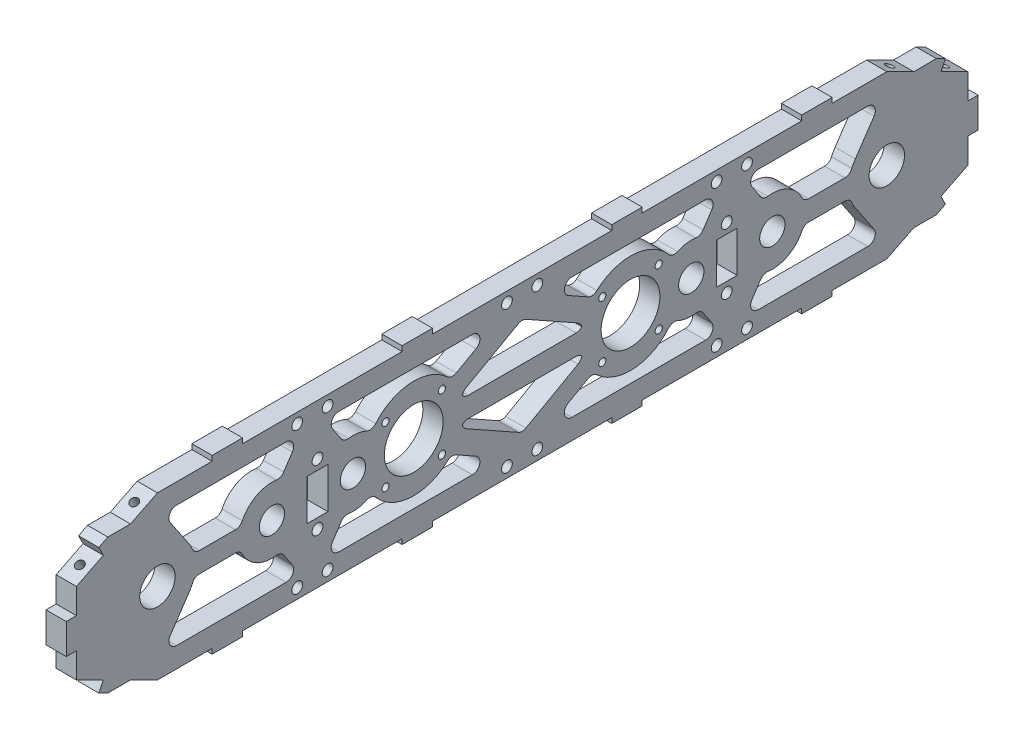
SolidWorks part; units mm, degrees
material "6061-T6 (SS)"
ref_plane "Front Plane" through (0, 0, 0) normal (0, 0, 1) x (1, 0, 0)
ref_plane "Top Plane" through (0, 0, 0) normal (0, 1, 0) x (1, 0, 0)
ref_plane "Right Plane" through (0, 0, 0) normal (1, 0, 0) x (0, 0, -1)
sketch "Sketch1" plane through (0, 0, 0) normal (1, 0, 0) x (0, 0, -1)
  line L0 (-160.655, 50.8) -> (93.345, 50.8)
  line L1 (93.345, 50.8) -> (93.345, -50.8)
  line L2 (93.345, -50.8) -> (-160.655, -50.8)
  line L3 (93.345, 0) -> (55.245, 50.8)
  line L4 (93.345, 0) -> (55.245, -50.8)
  circle A0 centre (0, 0) radius 38.1
  circle A1 centre (0, 0) radius 7.9375
  circle A2 centre (-38.1, 0) radius 7.9375
  circle A3 centre (-88.9, 0) radius 7.9375
  circle A4 centre (-88.9, 0) radius 39.751
  circle A5 centre (-38.1, 0) radius 25.4
  circle A6 centre (-160.655, 0) radius 11.1125
  circle A7 centre (-88.9, 0) radius 23.368
  circle A8 centre (-160.655, 0) radius 33.655
  circle A9 centre (-160.655, 0) radius 76.2
  circle A10 centre (-160.655, 0) radius 50.8
  dimension "D1" = 38.1
  dimension "D3" = 71.755
  dimension "D4" = 15.875
  dimension "D5" = 101.6
  dimension "D9" = 50.8
  dimension "D10" = 67.31
  dimension "D11" = 79.502
  dimension "D12" = 46.736
  dimension "D2" = 50.8
  dimension "D6" = 254
  dimension "D7" = 38.1
  dimension "D8" = 38.1
extrude "Boss-Extrude1" add sketch "Sketch1" along normal blind 12.7 contours A5 A0 A1 | A0 A5 | A10 A7 A9 A3 | A10 A7 A9 A4 | A7 A10 A4 | A7 A10 | A10 A4 A9 A7 | A9 A4 A5 A7 | A10 L2 A9 A4 | A4 A10 A8 | A8 A6 | A10 A4 A9 L0 | A9 A4 A5 A0 L2 L4 L3 L0 | A9 A3 A7 | A4 A5 | A0 A5 A4 A2 | A4 A8 region at (0, 24.069, -72.5203) region at (0, 42.9334, 118.4345) region at (0, 43.3242, 136.8815) region at (0, 26.7507, 103.5231) region at (0, 35.0406, 72.108) region at (0, -42.9334, 118.4345) region at (0, 0, 119.1262) region at (0, 24.4524, 42.4444) region at (0, 0, 55.9937) region at (0, 0, 97.9886) region at (0, 0, 76.9553) region at (0, -26.7507, 103.5231) region at (0, 0, 127.8393) region at (0, 0, 129.5966) region at (0, 0, 110.9718) region at (0, 0, 24.8917) region at (0, 34.9598, -12.3602)
hole_wizard "#8 Clearance Hole1" positions "Sketch3" profile "Sketch4" hole size "#8" standard "ANSI Inch" end condition through all
sketch "Sketch3" plane through (0, 0, 0) normal (-1, 0, 0) x (0, 0, 1)
  point P0 (-17.6911, 17.6911)
  point P3 (17.6911, 17.6911)
  point P6 (17.6911, -17.6911)
  point P9 (-17.6911, -17.6911)
sketch "Sketch4" plane through (0, 17.6911, -17.6911) normal (0, 1, 0) x (0, 0, 1)
  line L0 (0, 0) -> (0, 12.7)
  line L1 (0, 12.7) -> (2.2479, 12.7)
  line L2 (2.2479, 12.7) -> (2.2479, 0)
  line L5 (2.2479, 0) -> (0, 0)
  line L11 (0, -6.35) -> (0, 107.95) construction
  dimension "Thru Hole Dia." = 4.4958
  dimension "Thru Hole Depth" = 12.7
sketch "Sketch5" plane through (0, 0, 0) normal (-1, 0, 0) x (0, 0, 1)
  circle A0 centre (0, 0) radius 18.415
extrude "Cut-Extrude1" cut sketch "Sketch5" against normal through all
sketch "Sketch8" plane through (12.7, 0, 0) normal (1, 0, 0) x (0, 0, -1)
  line L0 (-160.655, 50.8) -> (-211.455, 25.4)
  line L1 (-211.455, 25.4) -> (-211.455, -25.4)
  line L2 (-211.455, -25.4) -> (-160.655, -50.8)
  line L3 (-160.655, -50.8) -> (-233.2397, -50.8)
  line L4 (-233.2397, -50.8) -> (-233.2397, 50.8)
  line L5 (-233.2397, 50.8) -> (-160.655, 50.8)
  line L6 (-211.455, 0) -> (-160.655, 0) construction
  arc A0 (-160.655, 50.8) -> (-160.655, -50.8) centre (-160.655, 0) ccw construction
  dimension "D1" = 50.8
extrude "Cut-Extrude3" cut sketch "Sketch8" against normal through all
sketch "Sketch9" plane through (12.7, 0, 0) normal (1, 0, 0) x (0, 0, -1)
  line L0 (-160.655, 50.8) -> (-211.455, 25.4)
  line L1 (-211.455, 25.4) -> (-211.455, 0)
  line L2 (-211.455, 0) -> (-211.455, -25.4)
  line L3 (-211.455, -25.4) -> (-160.655, -50.8)
  line L4 (-160.655, -50.8) -> (-160.655, -40.64)
  line L5 (-160.655, -40.64) -> (-202.7493, 0)
  line L6 (-202.7493, 0) -> (-160.655, 40.64)
  line L7 (-160.655, 40.64) -> (-160.655, 50.8)
  line L8 (-160.655, -50.8) -> (-201.295, -30.48) construction
  line L9 (-201.295, 30.48) -> (-160.655, 50.8) construction
  arc A0 (-201.295, 30.48) -> (-201.295, -30.48) centre (-160.655, 0) ccw construction
extrude "Boss-Extrude2" add sketch "Sketch9" against normal blind 12.7
sketch "Sketch10" plane through (0, 0, 0) normal (-1, 0, 0) x (0, 0, 1)
  line L0 (-67.945, -33.8667) -> (-67.945, 33.8667)
  line L1 (-93.345, 0) -> (-55.245, -50.8) construction
  line L3 (-93.345, 0) -> (-55.245, 50.8) construction
  line L4 (-67.945, 33.8667) -> (-93.345, 0)
  line L5 (-93.345, 0) -> (-67.945, -33.8667)
  dimension "D1" = 25.4
extrude "Cut-Extrude4" cut sketch "Sketch10" against normal through all
mirror "Mirror2" about plane through (12.7, -33.8667, -67.945) normal (0, 0, 1) of "Boss-Extrude1"
sketch "Sketch11" plane through (12.7, 0, 0) normal (1, 0, 0) x (0, 0, -1)
  line L0 (55.245, 50.8) -> (67.945, 33.8667)
  line L1 (67.945, 33.8667) -> (67.945, 50.8)
  line L2 (67.945, 50.8) -> (55.245, 50.8)
  line L3 (67.945, -33.8667) -> (55.245, -50.8)
  line L4 (67.945, -33.8667) -> (80.645, -50.8) construction
  line L5 (67.945, -33.8667) -> (55.245, -50.8) construction
  line L6 (55.245, -50.8) -> (67.945, -50.8)
  line L7 (67.945, -50.8) -> (67.945, -33.8667)
extrude "Boss-Extrude3" add sketch "Sketch11" against normal up to surface (12.7 mm away) up to face at (0, 0, -25.6117)
mirror "Mirror6" about plane through (-21.1667, 33.8667, -67.945) normal (0, 0, -1) of "Boss-Extrude3", "#8 Clearance Hole1", "Cut-Extrude1", "Cut-Extrude3", "Boss-Extrude2"
sketch "Sketch12" plane through (12.7, 0, 0) normal (1, 0, 0) x (0, 0, -1)
  line L36 (-160.655, 0) -> (-88.9, 0)
  line L37 (-88.9, 0) -> (-38.1, 0)
  line L38 (-38.1, 0) -> (0, 0)
  line L39 (0, 0) -> (135.89, 0)
  line L40 (135.89, 0) -> (173.99, 0)
  line L41 (173.99, 0) -> (224.79, 0)
  line L42 (224.79, 0) -> (296.545, 0)
  line L43 (-160.655, -6.35) -> (-88.9, -6.35)
  line L44 (334.645, 17.551) -> (293.5469, 38.1)
  line L45 (334.645, -17.551) -> (334.645, 17.551)
  line L46 (293.5469, -38.1) -> (334.645, -17.551)
  line L47 (-157.6569, -38.1) -> (293.5469, -38.1)
  line L48 (-198.755, -17.551) -> (-157.6569, -38.1)
  line L49 (-198.755, 17.551) -> (-198.755, -17.551)
  line L50 (-157.6569, 38.1) -> (-198.755, 17.551)
  line L51 (293.5469, 38.1) -> (-157.6569, 38.1)
  line L52 (334.645, 17.551) -> (293.5469, 38.1)
  line L53 (334.645, -17.551) -> (334.645, 17.551)
  line L54 (293.5469, -38.1) -> (334.645, -17.551)
  line L55 (-157.6569, -38.1) -> (293.5469, -38.1)
  line L56 (-198.755, -17.551) -> (-157.6569, -38.1)
  line L57 (-198.755, 17.551) -> (-198.755, -17.551)
  line L58 (-157.6569, 38.1) -> (-198.755, 17.551)
  line L59 (293.5469, 38.1) -> (-157.6569, 38.1)
  line L60 (-88.9, -6.35) -> (-38.1, -6.35)
  line L61 (-38.1, -6.35) -> (0, -6.35)
  line L62 (0, -6.35) -> (135.89, -6.35)
  line L63 (135.89, -6.35) -> (173.99, -6.35)
  line L64 (173.99, -6.35) -> (224.79, -6.35)
  line L65 (224.79, -6.35) -> (296.545, -6.35)
  line L66 (-160.655, 6.35) -> (-88.9, 6.35)
  line L67 (-88.9, 6.35) -> (-38.1, 6.35)
  line L68 (-38.1, 6.35) -> (0, 6.35)
  line L69 (0, 6.35) -> (135.89, 6.35)
  line L70 (135.89, 6.35) -> (173.99, 6.35)
  line L71 (173.99, 6.35) -> (224.79, 6.35)
  line L72 (224.79, 6.35) -> (296.545, 6.35)
  line L73 (-157.6569, 38.1) -> (-140.9232, 13.3301)
  line L74 (-157.6569, -38.1) -> (-140.9232, -13.3301)
  line L75 (293.5469, 38.1) -> (276.8132, 13.3301)
  line L76 (293.5469, -38.1) -> (276.8132, -13.3301)
  line L77 (-88.9, 0) -> (-63.5, 38.1)
  line L78 (-63.5, 38.1) -> (-38.1, 0)
  line L79 (-38.1, 0) -> (-63.5, -38.1)
  line L80 (-63.5, -38.1) -> (-88.9, 0)
  line L81 (173.99, 0) -> (199.39, 38.1)
  line L82 (199.39, 38.1) -> (224.79, 0)
  line L83 (224.79, 0) -> (199.39, -38.1)
  line L84 (199.39, -38.1) -> (173.99, 0)
  line L85 (-63.5, 6.35) -> (-63.5, 38.1) construction
  line L86 (-81.2682, 0) -> (-63.5, 26.6524)
  line L87 (-63.5, 26.6524) -> (-45.7318, 0)
  line L88 (-45.7318, 0) -> (-63.5, -26.6524)
  line L89 (-63.5, -26.6524) -> (-81.2682, 0)
  line L90 (181.6218, 0) -> (199.39, 26.6524)
  line L91 (199.39, 26.6524) -> (217.1582, 0)
  line L92 (217.1582, 0) -> (199.39, -26.6524)
  line L93 (199.39, -26.6524) -> (181.6218, 0)
  line L94 (-96.5318, 0) -> (-63.5, 49.5476)
  line L95 (-63.5, 49.5476) -> (-30.4682, 0)
  line L96 (-30.4682, 0) -> (-63.5, -49.5476)
  line L97 (-63.5, -49.5476) -> (-96.5318, 0)
  line L98 (166.3582, 0) -> (199.39, 49.5476)
  line L99 (199.39, 49.5476) -> (232.4218, 0)
  line L100 (232.4218, 0) -> (199.39, -49.5476)
  line L101 (199.39, -49.5476) -> (166.3582, 0)
  line L102 (0, 0) -> (67.945, 38.1)
  line L103 (67.945, 38.1) -> (135.89, 0)
  line L104 (135.89, 0) -> (67.945, -38.1)
  line L105 (67.945, -38.1) -> (0, 0)
  line L106 (12.983, 0) -> (67.945, 30.8198)
  line L107 (67.945, 30.8198) -> (122.907, 0)
  line L108 (122.907, 0) -> (67.945, -30.8198)
  line L109 (67.945, -30.8198) -> (12.983, 0)
  line L110 (-12.983, 0) -> (67.945, 45.3802)
  line L111 (67.945, 45.3802) -> (148.873, 0)
  line L112 (148.873, 0) -> (67.945, -45.3802)
  line L113 (67.945, -45.3802) -> (-12.983, 0)
  circle A5 centre (-160.655, 0) radius 23.8125
  circle A6 centre (-160.655, 0) radius 23.8125
  circle A8 centre (-88.9, 0) radius 20.6375
  circle A9 centre (-88.9, 0) radius 20.6375
  circle A11 centre (-38.1, 0) radius 20.6375
  circle A12 centre (-38.1, 0) radius 20.6375
  circle A14 centre (0, 0) radius 31.115
  circle A15 centre (0, 0) radius 31.115
  circle A17 centre (135.89, 0) radius 31.115
  circle A18 centre (135.89, 0) radius 31.115
  circle A20 centre (173.99, 0) radius 20.6375
  circle A21 centre (173.99, 0) radius 20.6375
  circle A23 centre (224.79, 0) radius 20.6375
  circle A24 centre (224.79, 0) radius 20.6375
  circle A26 centre (296.545, 0) radius 23.8125
  circle A27 centre (296.545, 0) radius 23.8125
  dimension "D10" = 6.35
  dimension "D12" = 6.35
  dimension "D14" = 6.35
  dimension "D1" = 12.7
  dimension "D2" = 12.7
  dimension "D3" = 12.7
  dimension "D4" = 12.7
  dimension "D5" = 12.7
  dimension "D6" = 12.7
  dimension "D7" = 12.7
  dimension "D8" = 12.7
  dimension "D9" = 12.7
  dimension "D11" = 6.35
  dimension "D13" = 6.35
  dimension "D15" = 6.35
extrude "Cut-Extrude5" cut sketch "Sketch12" against normal through all contours A9 L94 L59 L73 A6 L66 | A9 L43 A6 L74 L55 L97 | A15 L110 L59 L95 A12 | A15 A12 L96 L55 L113 | A18 L107 L106 A15 L69 | A18 L62 A15 L109 L108 | A21 L98 L59 L111 A18 | A21 A18 L112 L55 L101 | A27 L75 L59 L99 A24 L72 | A27 L65 A24 L100 L55 L76 region at (12.7, 25.2391, 116.6041) region at (12.7, -25.2391, 116.6041) region at (12.7, 31.2882, 6.6951) region at (12.7, -31.2882, 6.6951) region at (12.7, 31.2882, -142.5851) region at (12.7, -31.2882, -142.5851) region at (12.7, 14.6339, -67.945) region at (12.7, -14.6339, -67.945) region at (12.7, 25.2391, -252.4941) region at (12.7, -25.2391, -252.4941)
fillet "Fillet1" radius 4.7625 50 edges at (6.35, 6.35, -244.4263) (6.35, 19.8607, -219.1813) (6.35, 38.1, -207.0218) (6.35, 38.1, -293.5469) (6.35, 6.35, -273.5948) (6.35, -38.1, -207.0218) (6.35, -19.8607, -219.1813) (6.35, -6.35, -244.4263) (6.35, -6.35, -273.5948) (6.35, -38.1, -293.5469) (6.35, -19.8607, -179.5987) (6.35, -38.1, -80.928) (6.35, -20.4367, -112.4276) (6.35, -16.837, -162.056) (6.35, -38.1, -191.7582) (6.35, 16.837, -162.056) (6.35, 20.4367, -112.4276) (6.35, 38.1, -80.928) (6.35, 38.1, -191.7582) (6.35, 19.8607, -179.5987) (6.35, 6.35, -105.4299) (6.35, 9.3594, -29.674) (6.35, 30.8198, -67.945) (6.35, 9.3594, -106.216) (6.35, 6.35, -30.4601) (6.35, -9.3594, -106.216) (6.35, -30.8198, -67.945) (6.35, -6.35, -30.4601) (6.35, -6.35, -105.4299) (6.35, -9.3594, -29.674) (6.35, -20.4367, -23.4624) (6.35, -38.1, -54.962) (6.35, -19.8607, 43.7087) (6.35, -16.837, 26.166) (6.35, -38.1, 55.8682) (6.35, 16.837, 26.166) (6.35, 38.1, 55.8682) (6.35, 38.1, -54.962) (6.35, 20.4367, -23.4624) (6.35, 19.8607, 43.7087) (6.35, -19.8607, 83.2913) (6.35, -38.1, 71.1318) (6.35, -6.35, 137.7048) (6.35, -6.35, 108.5363) (6.35, -38.1, 157.6569) (6.35, 6.35, 108.5363) (6.35, 38.1, 157.6569) (6.35, 38.1, 71.1318) (6.35, 19.8607, 83.2913) (6.35, 6.35, 137.7048)
sketch "Sketch14" plane through (12.7, 0, 0) normal (1, 0, 0) x (0, 0, -1)
  line L0 (-53.975, 0) -> (0, 0) construction
  line L1 (202.565, 12.7) -> (189.865, 12.7)
  line L2 (202.565, 12.7) -> (202.565, -12.7)
  line L3 (202.565, -12.7) -> (189.865, -12.7)
  line L4 (189.865, 12.7) -> (189.865, -12.7)
  line L5 (-66.675, 12.7) -> (-53.975, 12.7)
  line L6 (-66.675, 12.7) -> (-66.675, -12.7)
  line L7 (-66.675, -12.7) -> (-53.975, -12.7)
  line L8 (-53.975, 12.7) -> (-53.975, -12.7)
  line L9 (0, 0) -> (135.89, 0) construction
  line L10 (135.89, 0) -> (189.865, 0) construction
  line L11 (-66.802, 12.827) -> (-53.848, 12.827)
  line L12 (-53.848, 12.827) -> (-53.848, -12.827)
  line L13 (-66.802, -12.827) -> (-53.848, -12.827)
  line L14 (-66.802, 12.827) -> (-66.802, -12.827)
  line L15 (202.692, 12.827) -> (189.738, 12.827)
  line L16 (189.738, 12.827) -> (189.738, -12.827)
  line L17 (202.692, -12.827) -> (189.738, -12.827)
  line L18 (202.692, 12.827) -> (202.692, -12.827)
  circle A0 centre (135.89, 0) radius 18.415 construction
  circle A1 centre (0, 0) radius 18.415 construction
  dimension "D1" = 66.675
  dimension "D2" = 66.675
  dimension "D3" = 12.7
  dimension "D4" = 12.7
  dimension "D5" = 25.4
  dimension "D6" = 25.4
  dimension "D7" = 0.127
  dimension "D8" = 0.127
extrude "Cut-Extrude6" cut sketch "Sketch14" against normal through all
hole_wizard "1/4 Clearance Hole1" positions "Sketch16" profile "Sketch15" hole size "1/4" standard "ANSI Inch" end condition through all
sketch "Sketch16" plane through (12.7, 0, 0) normal (1, 0, 0) x (0, 0, -1)
  line L0 (-60.325, 19.05) -> (196.215, 19.05) construction
  line L1 (196.215, 19.05) -> (196.215, -19.05) construction
  line L2 (196.215, -19.05) -> (-60.325, -19.05) construction
  line L3 (-60.325, -19.05) -> (-60.325, 19.05) construction
  line L5 (0, 0) -> (-60.325, 0) construction
  line L7 (135.89, 0) -> (196.215, 0) construction
  point P0 (-60.325, 19.05)
  point P2 (-60.325, -19.05)
  point P4 (196.215, -19.05)
  point P6 (196.215, 19.05)
  dimension "D1" = 60.325
  dimension "D2" = 38.1
sketch "Sketch15" plane through (12.7, 19.05, 60.325) normal (0, 1, 0) x (0, 0, -1)
  line L0 (0, 0) -> (0, 12.7)
  line L1 (0, 12.7) -> (3.3782, 12.7)
  line L2 (3.3782, 12.7) -> (3.3782, 0)
  line L5 (3.3782, 0) -> (0, 0)
  line L11 (0, -6.35) -> (0, 107.95) construction
  dimension "Thru Hole Dia." = 6.7564
  dimension "Thru Hole Depth" = 12.7
hole_wizard "1/4 Clearance Hole2" positions "Sketch18" profile "Sketch17" hole size "1/4" standard "ANSI Inch" end condition through all
sketch "Sketch18" plane through (12.7, 0, 0) normal (1, 0, 0) x (0, 0, -1)
  line L0 (-75.8316, 35.5847) -> (-51.1684, 35.5847) construction
  line L1 (-51.1684, 35.5847) -> (41.3394, 34.5413) construction
  line L2 (41.3394, 34.5413) -> (94.5506, 34.5413) construction
  line L3 (94.5506, 34.5413) -> (187.0584, 35.5847) construction
  line L4 (187.0584, 35.5847) -> (211.7216, 35.5847) construction
  line L10 (-63.5, 35.5847) -> (-63.5, 50.8) construction
  line L11 (-160.655, 50.8) -> (296.545, 50.8) construction
  line L13 (67.945, 34.5413) -> (67.945, 50.8) construction
  line L15 (199.39, 35.5847) -> (199.39, 50.8) construction
  line L16 (-173.355, 44.45) -> (-73.025, 44.45) construction
  line L17 (-211.455, 25.4) -> (-160.655, 50.8) construction
  line L18 (-73.025, 44.45) -> (-63.5, 44.45) construction
  line L19 (-63.5, 44.45) -> (-53.975, 44.45) construction
  line L20 (-53.975, 44.45) -> (58.42, 44.45) construction
  line L21 (58.42, 44.45) -> (67.945, 44.45) construction
  line L22 (67.945, 44.45) -> (77.47, 44.45) construction
  line L23 (77.47, 44.45) -> (189.865, 44.45) construction
  line L24 (189.865, 44.45) -> (199.39, 44.45) construction
  line L25 (199.39, 44.45) -> (208.915, 44.45) construction
  arc A0 (-76.0679, 30.6957) -> (-80.0306, 38.1) centre (-80.0306, 33.3375) ccw construction
  arc A1 (-46.9694, 38.1) -> (-50.9321, 30.6957) centre (-46.9694, 33.3375) ccw construction
  arc A2 (39.0609, 29.1835) -> (36.7316, 38.1) centre (36.7316, 33.3375) ccw construction
  arc A3 (99.1584, 38.1) -> (96.8291, 29.1835) centre (99.1584, 33.3375) ccw construction
  arc A4 (186.8221, 30.6957) -> (182.8594, 38.1) centre (182.8594, 33.3375) ccw construction
  arc A5 (215.9206, 38.1) -> (211.9579, 30.6957) centre (215.9206, 33.3375) ccw construction
  point P50 (-73.025, 44.45)
  point P52 (-53.975, 44.45)
  point P54 (58.42, 44.45)
  point P56 (77.47, 44.45)
  point P58 (189.865, 44.45)
  point P60 (208.915, 44.45)
  dimension "D1" = 6.35
  dimension "D2" = 9.525
sketch "Sketch17" plane through (12.7, 44.45, 73.025) normal (0, 1, 0) x (0, 0, -1)
  line L0 (0, 0) -> (0, 12.7)
  line L1 (0, 12.7) -> (3.3782, 12.7)
  line L2 (3.3782, 12.7) -> (3.3782, 0)
  line L5 (3.3782, 0) -> (0, 0)
  line L11 (0, -6.35) -> (0, 107.95) construction
  dimension "Thru Hole Dia." = 6.7564
  dimension "Thru Hole Depth" = 12.7
sketch "Sketch19" plane through (12.7, 0, 0) normal (1, 0, 0) x (0, 0, -1)
  line L0 (-73.025, 44.45) -> (-160.655, 44.45) construction
  line L1 (-160.655, 44.45) -> (-160.655, 50.8) construction
  line L2 (-53.975, 44.45) -> (58.42, 44.45) construction
  line L3 (58.42, 44.45) -> (77.47, 44.45) construction
  line L4 (77.47, 44.45) -> (189.865, 44.45) construction
  line L5 (189.865, 44.45) -> (208.915, 44.45) construction
  line L6 (208.915, 44.45) -> (296.545, 44.45) construction
  line L7 (296.545, 44.45) -> (296.545, 50.8) construction
  line L8 (-116.84, 44.45) -> (-116.84, 50.8) construction
  line L9 (-160.655, 50.8) -> (296.545, 50.8) construction
  line L10 (2.2225, 44.45) -> (2.2225, 50.8) construction
  line L12 (133.6675, 44.45) -> (133.6675, 50.8) construction
  line L13 (-126.365, 50.8) -> (-107.315, 50.8)
  line L14 (252.73, 44.45) -> (252.73, 50.8) construction
  line L15 (-126.365, 50.8) -> (-126.365, 53.975)
  line L16 (-126.365, 53.975) -> (-107.315, 53.975)
  line L17 (-107.315, 50.8) -> (-107.315, 53.975)
  line L18 (-7.3025, 50.8) -> (11.7475, 50.8)
  line L19 (-7.3025, 50.8) -> (-7.3025, 53.975)
  line L20 (-7.3025, 53.975) -> (11.7475, 53.975)
  line L21 (11.7475, 50.8) -> (11.7475, 53.975)
  line L22 (124.1425, 50.8) -> (143.1925, 50.8)
  line L23 (124.1425, 50.8) -> (124.1425, 53.975)
  line L24 (124.1425, 53.975) -> (143.1925, 53.975)
  line L25 (143.1925, 50.8) -> (143.1925, 53.975)
  line L26 (243.205, 50.8) -> (262.255, 50.8)
  line L27 (243.205, 50.8) -> (243.205, 53.975)
  line L28 (243.205, 53.975) -> (262.255, 53.975)
  line L29 (262.255, 50.8) -> (262.255, 53.975)
  dimension "D1" = 19.05
  dimension "D2" = 3.175
extrude "Boss-Extrude4" add sketch "Sketch19" against normal up to surface (12.7 mm away) up to face at (0, 44.45, 69.6468)
mirror "Mirror7" about plane through (0, 0, 0) normal (0, 1, 0) of "Boss-Extrude4", "1/4 Clearance Hole2"
sketch "Sketch20" plane through (12.7, 0, 0) normal (1, 0, 0) x (0, 0, -1)
  line L0 (347.345, 25.4) -> (347.345, -25.4) construction
  line L1 (347.345, 9.525) -> (353.695, 9.525)
  line L2 (347.345, 9.525) -> (347.345, -9.525)
  line L3 (347.345, -9.525) -> (353.695, -9.525)
  line L4 (353.695, 9.525) -> (353.695, -9.525)
  line L5 (313.4256, 42.3597) -> (316.2654, 48.0393)
  line L6 (347.345, 25.4) -> (296.545, 50.8) construction
  line L7 (316.2654, 48.0393) -> (333.3042, 39.5199)
  line L8 (333.3042, 39.5199) -> (330.4644, 33.8403)
  line L9 (330.4644, 33.8403) -> (313.4256, 42.3597)
  line L10 (330.4644, -33.8403) -> (333.3042, -39.5199)
  line L11 (296.545, -50.8) -> (347.345, -25.4) construction
  line L12 (333.3042, -39.5199) -> (316.2654, -48.0393)
  line L13 (316.2654, -48.0393) -> (313.4256, -42.3597)
  line L14 (313.4256, -42.3597) -> (330.4644, -33.8403)
  line L15 (-177.5356, 42.3597) -> (-180.3754, 48.0393)
  line L16 (-211.455, 25.4) -> (-160.655, 50.8) construction
  line L17 (-180.3754, 48.0393) -> (-197.4142, 39.5199)
  line L18 (-197.4142, 39.5199) -> (-194.5744, 33.8403)
  line L19 (-194.5744, 33.8403) -> (-177.5356, 42.3597)
  line L20 (-177.5356, -42.3597) -> (-180.3754, -48.0393)
  line L21 (-160.655, -50.8) -> (-211.455, -25.4) construction
  line L22 (-180.3754, -48.0393) -> (-197.4142, -39.5199)
  line L23 (-197.4142, -39.5199) -> (-194.5744, -33.8403)
  line L24 (-194.5744, -33.8403) -> (-177.5356, -42.3597)
  line L25 (-211.455, 25.4) -> (-211.455, -25.4) construction
  line L26 (-211.455, 9.525) -> (-217.805, 9.525)
  line L27 (-211.455, 9.525) -> (-211.455, -9.525)
  line L28 (-211.455, -9.525) -> (-217.805, -9.525)
  line L29 (-217.805, 9.525) -> (-217.805, -9.525)
  line L30 (313.4256, 42.3597) -> (327.6246, 42.3597)
  line L31 (313.4256, -42.3597) -> (327.6246, -42.3597)
  line L32 (-177.5356, -42.3597) -> (-191.7346, -42.3597)
  line L33 (-177.5356, 42.3597) -> (-191.7346, 42.3597)
  point P36 (-186.055, 38.1)
  point P37 (-211.455, 0)
  point P38 (-186.055, -38.1)
  point P39 (321.945, -38.1)
  point P40 (347.345, 0)
  point P41 (321.945, 38.1)
  dimension "D1" = 6.35
  dimension "D2" = 19.05
extrude "Boss-Extrude5" add sketch "Sketch20" against normal up to surface (12.7 mm away) contours L19 L33 L17 L18 | L26 L29 L28 L27 | L32 L24 L23 L22 | L14 L31 L12 L10 | L4 L1 L2 L3 | L30 L9 L8 L7 region at (12.7, 0, -350.52) region at (12.7, 39.2833, -325.4948) region at (12.7, -39.2833, -325.4948) region at (12.7, 39.2833, 189.6048) region at (12.7, -39.2833, 189.6048) region at (12.7, 0, 214.63) up to face at (0, -44.45, 69.6468)
hole_wizard "1/4-20 Tapped Hole1" positions "Sketch22" profile "Sketch21" tap size "1/4-20" standard "ANSI Inch"
sketch "Sketch22" plane through (0, 104.902, 52.451) normal (0, 0.8944, 0.4472) x (1, 0, 0)
  point P0 (6.35, -130.1469)
  point P2 (6.35, -168.2469)
sketch "Sketch21" plane through (6.35, 46.6985, 168.8579) normal (1, 0, 0) x (0, -0.4472, 0.8944)
  line L0 (0, 0) -> (0, 24.3938)
  line L1 (0, 24.3938) -> (2.5527, 22.86)
  line L2 (2.5527, 22.86) -> (2.5527, 0)
  line L5 (2.5527, 0) -> (0, 0)
  line L10 (0, 24.3938) -> (-2.5527, 22.86) construction
  line L11 (0, -6.35) -> (0, 107.95) construction
  dimension "Tap Drill Dia." = 5.1054
  dimension "Tap Drill Depth" = 22.86
  dimension "Drill Angle" = 118
hole_wizard "1/4-20 Tapped Hole2" positions "Sketch24" profile "Sketch23" tap size "1/4-20" standard "ANSI Inch"
sketch "Sketch24" plane through (0, -104.902, 52.451) normal (0, -0.8944, 0.4472) x (-1, 0, 0)
  point P0 (-6.35, -168.2469)
  point P2 (-6.35, -130.1469)
sketch "Sketch23" plane through (6.35, -29.6597, 202.9356) normal (1, 0, 0) x (0, -0.4472, -0.8944)
  line L0 (0, 0) -> (0, 24.3938)
  line L1 (0, 24.3938) -> (2.5527, 22.86)
  line L2 (2.5527, 22.86) -> (2.5527, 0)
  line L5 (2.5527, 0) -> (0, 0)
  line L10 (0, 24.3938) -> (-2.5527, 22.86) construction
  line L11 (0, -6.35) -> (0, 107.95) construction
  dimension "Tap Drill Dia." = 5.1054
  dimension "Tap Drill Depth" = 22.86
  dimension "Drill Angle" = 118
hole_wizard "1/4-20 Tapped Hole3" positions "Sketch26" profile "Sketch25" tap size "1/4-20" standard "ANSI Inch"
sketch "Sketch26" plane through (0, 159.258, -79.629) normal (0, 0.8944, -0.4472) x (1, 0, 0)
  point P0 (6.35, 251.6906)
  point P2 (6.35, 289.7906)
sketch "Sketch25" plane through (6.35, 46.6985, -304.7479) normal (1, 0, 0) x (0, 0.4472, 0.8944)
  line L0 (0, 0) -> (0, 24.3938)
  line L1 (0, 24.3938) -> (2.5527, 22.86)
  line L2 (2.5527, 22.86) -> (2.5527, 0)
  line L5 (2.5527, 0) -> (0, 0)
  line L10 (0, 24.3938) -> (-2.5527, 22.86) construction
  line L11 (0, -6.35) -> (0, 107.95) construction
  dimension "Tap Drill Dia." = 5.1054
  dimension "Tap Drill Depth" = 22.86
  dimension "Drill Angle" = 118
hole_wizard "1/4-20 Tapped Hole4" positions "Sketch28" profile "Sketch27" tap size "1/4-20" standard "ANSI Inch"
sketch "Sketch28" plane through (0, -159.258, -79.629) normal (0, -0.8944, -0.4472) x (-1, 0, 0)
  point P0 (-6.35, 289.7906)
  point P2 (-6.35, 251.6906)
sketch "Sketch27" plane through (6.35, -29.6597, -338.8256) normal (1, 0, 0) x (0, 0.4472, -0.8944)
  line L0 (0, 0) -> (0, 24.3938)
  line L1 (0, 24.3938) -> (2.5527, 22.86)
  line L2 (2.5527, 22.86) -> (2.5527, 0)
  line L5 (2.5527, 0) -> (0, 0)
  line L10 (0, 24.3938) -> (-2.5527, 22.86) construction
  line L11 (0, -6.35) -> (0, 107.95) construction
  dimension "Tap Drill Dia." = 5.1054
  dimension "Tap Drill Depth" = 22.86
  dimension "Drill Angle" = 118
